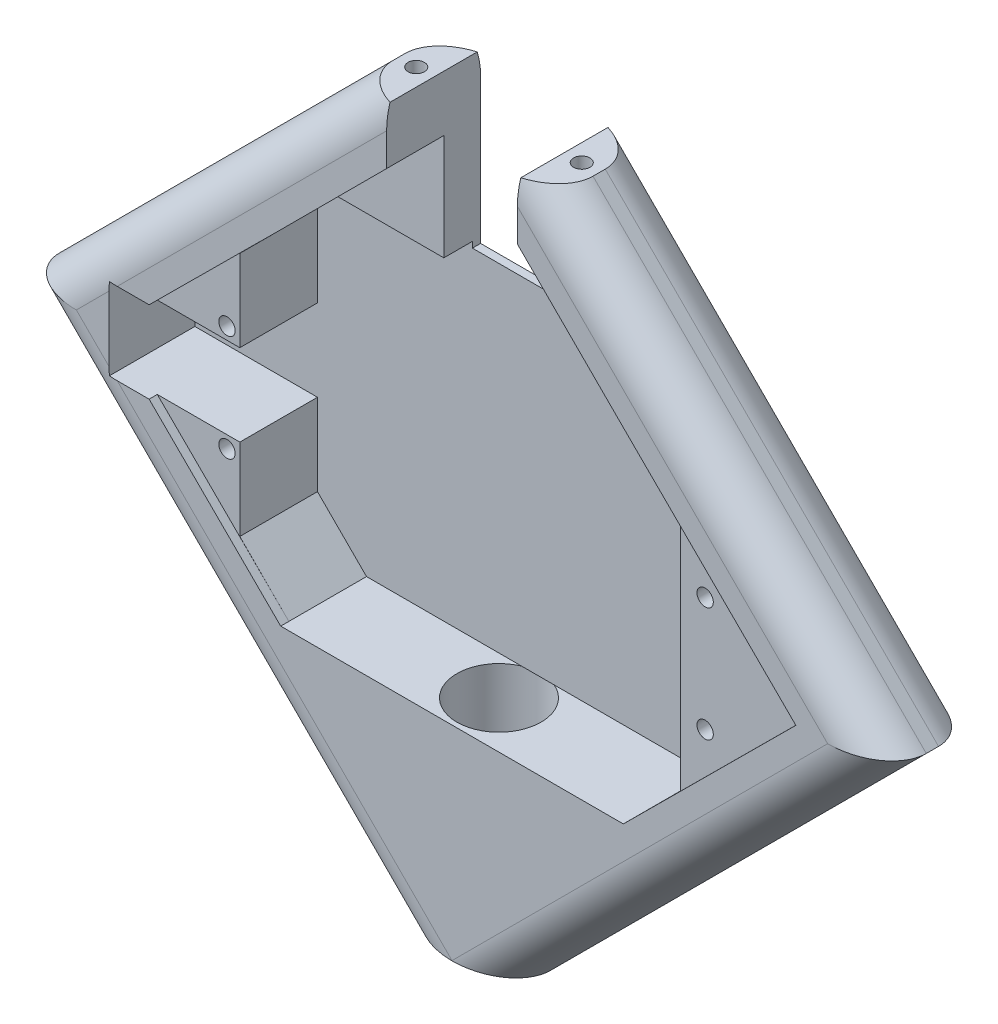
SolidWorks part; units mm, degrees
ref_plane "Front" through (0, 0, 0) normal (0, 0, 1) x (1, 0, 0)
ref_plane "Top" through (0, 0, 0) normal (0, 1, 0) x (1, 0, 0)
ref_plane "Right" through (0, 0, 0) normal (1, 0, 0) x (0, 0, -1)
sketch "Sketch1" plane through (0, 0, 0) normal (0, 0, 1) x (1, 0, 0)
  line L0 (0, 53.03) -> (49.4072, 3.6228)
  line L1 (56.6528, 3.6228) -> (106.06, 53.03)
  line L3 (40.78, 93.81) -> (0, 53.03)
  line L4 (40.78, 93.81) -> (45.03, 93.81)
  line L5 (65.28, 93.81) -> (106.06, 53.03)
  line L6 (45.03, 93.81) -> (45.03, 73.31)
  line L7 (45.03, 73.31) -> (61.03, 73.31)
  line L8 (61.03, 73.31) -> (61.03, 93.81)
  line L9 (61.03, 93.81) -> (65.28, 93.81)
  line L10 (49.4072, 3.6228) -> (56.6528, 3.6228)
  point P26 (49.4072, 3.6228)
extrude "Boss-Extrude1" add sketch "Sketch1" along normal blind 11.5
sketch "Sketch5" plane through (0, 0, 11.5) normal (0, 0, 1) x (1, 0, 0)
  line L11 (0, 53.03) -> (11.07, 53.03) construction
  line L12 (26.07, 68.03) -> (32.07, 74.03)
  line L13 (32.07, 32.03) -> (73.99, 32.03)
  line L14 (26.07, 38.03) -> (26.07, 48.03)
  line L15 (32.07, 74.03) -> (73.99, 74.03)
  line L16 (79.99, 38.03) -> (79.99, 68.03)
  line L17 (29.3294, 34.7706) -> (76.7306, 71.2894) construction
  line L18 (29.3294, 71.2894) -> (76.7306, 34.7706) construction
  line L19 (73.99, 74.03) -> (79.99, 68.03)
  line L20 (26.07, 38.03) -> (32.07, 32.03)
  line L21 (73.99, 32.03) -> (79.99, 38.03)
  line L22 (11.07, 58.03) -> (26.07, 58.03)
  line L23 (11.07, 58.03) -> (11.07, 48.03)
  line L24 (11.07, 48.03) -> (26.07, 48.03)
  line L25 (26.07, 58.03) -> (26.07, 68.03)
  line L26 (53.03, 53.03) -> (106.06, 53.03) construction
  point P2 (53.03, 53.03)
  point P3 (73.99, 32.03)
  point P5 (73.99, 74.03)
  point P6 (11.07, 58.03)
  point P7 (26.07, 68.03)
  point P9 (32.07, 74.03)
  point P12 (79.99, 68.03)
  point P18 (79.99, 38.03)
  point P19 (26.07, 38.03)
  point P20 (32.07, 32.03)
  point P26 (11.07, 48.03)
extrude "Cut-Extrude1" cut sketch "Sketch5" against normal blind 10.5
sketch "Sketch10" plane through (0, 0, 0) normal (0, 1, 0) x (1, 0, 0)
  circle A0 centre (42.905, -5.75) radius 1
  circle A1 centre (63.155, -5.75) radius 1
  point P4 (0, 0)
  point P5 (0, 0)
  point P6 (0, 0)
  point P7 (0, 0)
  point P8 (0, 0)
extrude "Cut-Extrude3" cut sketch "Sketch10" against normal blind 3 from offset 93.81
sketch "Sketch11" plane through (0, 3.6228, 0) normal (0, -1, 0) x (1, 0, 0)
  circle A0 centre (53.03, 5.75) radius 5.15
  point P2 (0, 0)
extrude "Cut-Extrude4" cut sketch "Sketch11" against normal up to surface (28.4072 mm away) contours A0 up to face at (53.03, 32.03, 6.25)
sketch "Sketch13" plane through (0, 0, 0) normal (0, 0, 1) x (1, 0, 0)
  line L13 (73.99, 74.03) -> (61.03, 86.99)
  line L14 (61.03, 93.81) -> (61.03, 74.03) construction
  line L15 (61.03, 86.99) -> (61.03, 74.03)
  line L16 (61.03, 74.03) -> (73.99, 74.03)
  line L17 (32.07, 74.03) -> (45.03, 86.99)
  line L18 (45.03, 74.03) -> (45.03, 93.81) construction
  line L19 (45.03, 86.99) -> (45.03, 74.03)
  line L20 (45.03, 74.03) -> (32.07, 74.03)
  point P0 (6.2219, 53.0305)
  point P1 (33.0257, 53.03)
extrude "Cut-Extrude6" cut sketch "Sketch13" against normal blind 7 from offset 11.5
sketch "Sketch17" plane through (0, 0, 0) normal (0, 0, 1) x (1, 0, 0)
  circle A0 centre (24.5, 59.53) radius 1
  circle A1 centre (24.5, 46.53) radius 1
  circle A2 centre (83, 60.03) radius 1
  circle A3 centre (83, 46.03) radius 1
extrude "Cut-Extrude10" cut sketch "Sketch17" against normal blind 7 from surface starting at face at (46.138, 57.5413, 11.5)
sketch "Sketch19" plane through (0, 0, 0) normal (0, 0, 1) x (1, 0, 0)
  line L0 (13.96, 56.03) -> (13.96, 50.03)
  line L1 (13.96, 50.03) -> (32.07, 32.03)
  line L2 (32.07, 32.03) -> (73.99, 32.03)
  line L3 (73.99, 32.03) -> (95.1, 53.03)
  line L4 (95.1, 53.03) -> (73.99, 74.03)
  line L5 (73.99, 74.03) -> (32.07, 74.03)
  line L6 (32.07, 74.03) -> (13.96, 56.03)
  point P0 (13.96, 56.03)
  point P1 (13.96, 50.03)
  point P4 (95.1, 53.03)
  point P11 (73.99, 74.03)
  point P12 (32.07, 74.03)
  point P13 (32.07, 32.03)
  point P14 (73.99, 32.03)
extrude "Cut-Extrude11" cut sketch "Sketch19" against normal blind 1 from surface starting at face at (25.5, 46.53, 11.5)
fillet "Fillet1" radius 5 4 edges at (81.3564, 28.3264, 11.5) (24.7036, 28.3264, 11.5) (20.39, 73.42, 11.5) (85.67, 73.42, 11.5)
fillet "Fillet2" radius 5 4 edges at (20.39, 73.42, 0) (24.7036, 28.3264, 0) (81.3564, 28.3264, 0) (85.67, 73.42, 0)
sketch "Sketch22" plane through (0, 0, 0) normal (0, 0, 1) x (1, 0, 0)
  line L1 (-66.1598, -7.0357) -> (66.1598, -7.0357)
  line L2 (-66.1598, -7.0357) -> (-66.1598, 7.0357)
  line L3 (-66.1598, 7.0357) -> (66.1598, 7.0357)
  line L4 (66.1598, -7.0357) -> (66.1598, 7.0357)
  line L5 (-66.1598, -7.0357) -> (66.1598, 7.0357) construction
  line L6 (-66.1598, 7.0357) -> (66.1598, -7.0357) construction
  point P0 (0, 0)
extrude "Cut-Extrude13" cut sketch "Sketch22" along normal through all
